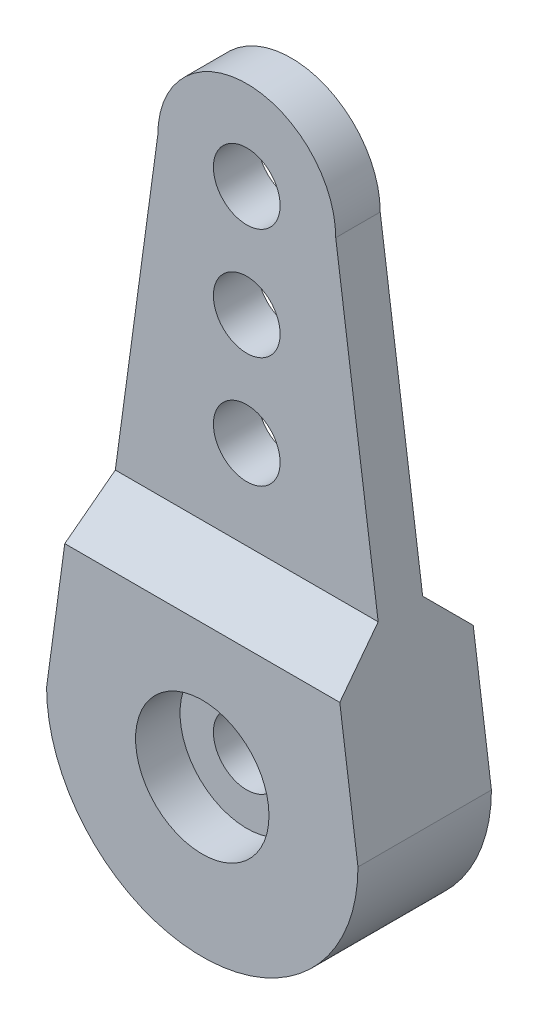
SolidWorks part; units mm, degrees
ref_plane "Front Plane" through (0, 0, 0) normal (0, 0, 1) x (1, 0, 0)
ref_plane "Top Plane" through (0, 0, 0) normal (0, 1, 0) x (1, 0, 0)
ref_plane "Right Plane" through (0, 0, 0) normal (1, 0, 0) x (0, 0, -1)
sketch "Sketch1" plane through (0, 0, 0) normal (0, 0, 1) x (1, 0, 0)
  line L0 (-7, 0) -> (-4, 22)
  line L1 (7, 0) -> (4, 22)
  arc A2 (4, 22) -> (-4, 22) centre (0, 22) ccw
  arc A3 (-7, 0) -> (7, 0) centre (0, 0) ccw
  dimension "D1" = 7
  dimension "D2" = 4
  dimension "D3" = 22
extrude "Boss-Extrude1" add sketch "Sketch1" along normal mid plane 2
sketch "Sketch2" plane through (0, 0, 0) normal (0, 0, 1) x (1, 0, 0)
  line L4 (0, -7) -> (8.7632, -7) construction
  line L5 (-5.9091, 8) -> (5.9091, 8)
  line L6 (7, 0) -> (4, 22) construction
  line L7 (-4, 22) -> (-7, 0) construction
  line L8 (7, 0) -> (5.9091, 8)
  line L9 (-5.9091, 8) -> (-7, 0)
  circle A2 centre (0, 0) radius 3
  arc A4 (-7, 0) -> (7, 0) centre (0, 0) ccw construction
  arc A5 (-7, 0) -> (7, 0) centre (0, 0) ccw
  dimension "D2" = 6
  dimension "D1" = 15
extrude "Boss-Extrude2" add sketch "Sketch2" along normal mid plane 6
chamfer "Chamfer1" distance 2 angle 45 2 edges at (0, 8, -3) (0, 8, 3)
sketch "Sketch3" plane through (0, 0, 1) normal (0, 0, 1) x (1, 0, 0)
  line L2 (0, 22) -> (0, 17) construction
  circle A3 centre (0, 22) radius 1.5
  circle A4 centre (0, 17) radius 1.5
  circle A5 centre (0, 12) radius 1.5
  dimension "D4" = 3
  dimension "D6" = 5
  dimension "D5" = 3
extrude "Cut-Extrude1" cut sketch "Sketch3" against normal through all
sketch "Sketch4" plane through (0, 0, 1) normal (0, 0, 1) x (1, 0, 0)
  circle A0 centre (0, 0) radius 1.5
  dimension "D1" = 3
extrude "Cut-Extrude2" cut sketch "Sketch4" against normal through all
